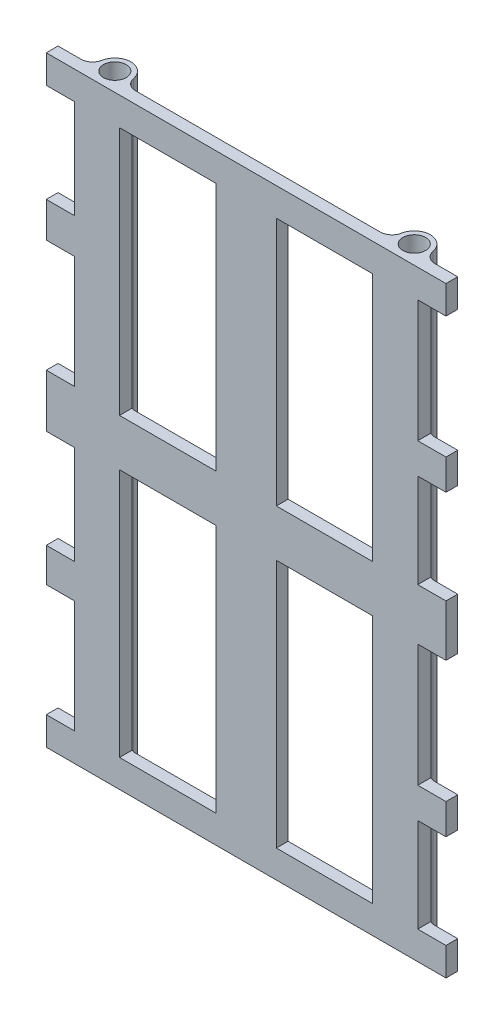
SolidWorks part; units mm, degrees
material "E-Glass Fiber"
ref_plane "Front Plane" through (0, 0, 0) normal (0, 0, 1) x (1, 0, 0)
ref_plane "Top Plane" through (0, 0, 0) normal (0, 1, 0) x (1, 0, 0)
ref_plane "Right Plane" through (0, 0, 0) normal (1, 0, 0) x (0, 0, -1)
other "Center of Mass"
sketch "Sketch1" plane through (0, 0, 0) normal (0, 1, 0) x (1, 0, 0)
  line L19 (85, -5) -> (85, 0)
  line L20 (85, -5) -> (-85, -5)
  line L24 (85, 0) -> (75.3042, 0)
  line L25 (-85, -5) -> (-85, 0)
  line L26 (85, -5) -> (-85, 0) construction
  line L27 (85, 0) -> (-85, -5) construction
  line L28 (0, 0) -> (0, -5) construction
  line L29 (-75.3042, 0) -> (-85, 0)
  line L30 (52.0558, 0) -> (-52.0558, 0)
  circle A29 centre (-63.68, 2.83) radius 4.825
  arc A30 (-69.8906, 0) -> (-57.4694, 0) centre (-63.68, 2.83) ccw construction
  arc A31 (-75.3042, 0) -> (-70.3891, 4.0825) centre (-75.3042, 5) ccw
  arc A32 (-56.9709, 4.0825) -> (-52.0558, 0) centre (-52.0558, 5) ccw
  arc A33 (-56.9709, 4.0825) -> (-70.3891, 4.0825) centre (-63.68, 2.83) ccw
  arc A34 (69.8906, 0) -> (57.4694, 0) centre (63.68, 2.83) cw construction
  arc A35 (56.9709, 4.0825) -> (70.3891, 4.0825) centre (63.68, 2.83) cw
  arc A36 (56.9709, 4.0825) -> (52.0558, 0) centre (52.0558, 5) cw
  arc A37 (75.3042, 0) -> (70.3891, 4.0825) centre (75.3042, 5) cw
  circle A38 centre (63.68, 2.83) radius 4.825
  point P1 (0, -2.5)
  dimension "D3" = 9.65
  dimension "D4" = 7.83
  dimension "D5" = 63.68
  dimension "D6" = 13.65
  dimension "D1" = 5
  dimension "D2" = 170
extrude "Boss-Extrude1" add sketch "Sketch1" along normal blind 255.8
sketch "Sketch2" plane through (0, 0, 0) normal (0, 0, -1) x (-1, 0, 0)
  line L0 (-85, 127.9) -> (85, 127.9) construction
  line L1 (-53.855, 11.8) -> (-12.855, 11.8)
  line L2 (-53.855, 11.8) -> (-53.855, 117.8)
  line L3 (-53.855, 243.8) -> (-12.855, 243.8)
  line L4 (-12.855, 11.8) -> (-12.855, 117.8)
  line L5 (-53.855, 11.8) -> (-12.855, 243.8) construction
  line L6 (-53.855, 243.8) -> (-12.855, 11.8) construction
  line L7 (-52.0558, 255.8) -> (52.0558, 255.8) construction
  line L8 (-12.855, 137.8) -> (-12.855, 243.8)
  line L9 (0, 255.8) -> (0, 0) construction
  line L10 (-93, 178.9) -> (-73, 178.9)
  line L11 (53.855, 11.8) -> (12.855, 11.8)
  line L12 (53.855, 11.8) -> (53.855, 117.8)
  line L13 (53.855, 243.8) -> (12.855, 243.8)
  line L14 (12.855, 11.8) -> (12.855, 117.8)
  line L15 (53.855, 11.8) -> (12.855, 243.8) construction
  line L16 (53.855, 243.8) -> (12.855, 11.8) construction
  line L17 (-58.855, 0) -> (-58.855, 255.8) construction
  line L18 (58.855, 255.8) -> (58.855, 0) construction
  line L19 (12.855, 137.8) -> (12.855, 243.8)
  line L20 (-53.855, 117.8) -> (-12.855, 117.8)
  line L22 (-53.855, 137.8) -> (-12.855, 137.8)
  line L24 (12.855, 137.8) -> (53.855, 137.8)
  line L25 (12.855, 117.8) -> (53.855, 117.8)
  line L26 (-53.855, 137.8) -> (-53.855, 243.8)
  line L27 (53.855, 137.8) -> (53.855, 243.8)
  line L28 (-93, 178.9) -> (-93, 138.9)
  line L29 (-93, 138.9) -> (-73, 138.9)
  line L30 (-73, 178.9) -> (-73, 138.9)
  line L31 (-93, 178.9) -> (-73, 138.9) construction
  line L32 (-93, 138.9) -> (-73, 178.9) construction
  line L33 (-85, 255.8) -> (-85, 0) construction
  line L34 (85, 255.8) -> (85, 0) construction
  line L35 (-93, 52) -> (-73, 52)
  line L36 (-73, 191.9) -> (-93, 191.9)
  line L37 (-73, 191.9) -> (-73, 243.8)
  line L38 (-73, 243.8) -> (-93, 243.8)
  line L39 (-93, 191.9) -> (-93, 243.8)
  line L40 (-73, 191.9) -> (-93, 243.8) construction
  line L41 (-73, 243.8) -> (-93, 191.9) construction
  line L42 (-93, 52) -> (-93, 12)
  line L43 (-93, 12) -> (-73, 12)
  line L44 (-73, 52) -> (-73, 12)
  line L53 (-93, 52) -> (-73, 12) construction
  line L54 (-93, 12) -> (-73, 52) construction
  line L55 (-73, 65) -> (-93, 65)
  line L56 (-73, 65) -> (-73, 117)
  line L57 (-73, 117) -> (-93, 117)
  line L58 (-93, 65) -> (-93, 117)
  line L59 (-73, 65) -> (-93, 117) construction
  line L60 (-73, 117) -> (-93, 65) construction
  line L61 (75.3042, 255.8) -> (85, 255.8) construction
  line L62 (-85, 0) -> (-75.3042, 0) construction
  line L67 (93, 201.8) -> (73, 201.8)
  line L68 (93, 201.8) -> (93, 243.8)
  line L73 (93, 243.8) -> (73, 243.8)
  line L74 (73, 201.8) -> (73, 243.8)
  line L75 (-85, 255.8) -> (-75.3042, 255.8) construction
  line L76 (93, 74.4) -> (73, 74.4)
  line L77 (93, 201.8) -> (73, 243.8) construction
  line L78 (93, 243.8) -> (73, 201.8) construction
  line L83 (73, 138.9) -> (93, 138.9)
  line L84 (73, 138.9) -> (73, 186.8)
  line L85 (73, 186.8) -> (93, 186.8)
  line L86 (93, 138.9) -> (93, 186.8)
  line L87 (73, 138.9) -> (93, 186.8) construction
  line L88 (73, 186.8) -> (93, 138.9) construction
  line L89 (93, 74.4) -> (93, 116.4)
  line L90 (93, 116.4) -> (73, 116.4)
  line L91 (73, 74.4) -> (73, 116.4)
  line L92 (93, 74.4) -> (73, 116.4) construction
  line L93 (93, 116.4) -> (73, 74.4) construction
  line L94 (73, 12) -> (93, 12)
  line L95 (73, 12) -> (73, 59.9)
  line L96 (73, 59.9) -> (93, 59.9)
  line L97 (93, 12) -> (93, 59.9)
  line L98 (73, 12) -> (93, 59.9) construction
  line L99 (73, 59.9) -> (93, 12) construction
  line L100 (75.3042, 0) -> (85, 0) construction
  point P0 (-33.355, 127.8)
  point P5 (-83, 158.9)
  point P14 (33.355, 127.8)
  point P23 (0, 127.8)
  point P39 (-83, 217.85)
  point P44 (-83, 32)
  point P49 (-83, 91)
  point P54 (83, 222.8)
  point P61 (83, 162.85)
  point P70 (83, 95.4)
  point P75 (83, 35.95)
  dimension "D1" = 12
  dimension "D2" = 5
  dimension "D3" = 41
  dimension "D4" = 12
  dimension "D5" = 5
  dimension "D6" = 41
  dimension "D7" = 20
  dimension "D8" = 11
  dimension "D9" = 40
  dimension "D10" = 73
  dimension "D11" = 20
  dimension "D12" = 13
  dimension "D13" = 12
  dimension "D14" = 40
  dimension "D15" = 20
  dimension "D16" = 13
  dimension "D17" = 52
  dimension "D18" = 73
  dimension "D19" = 20
  dimension "D20" = 12
  dimension "D21" = 12
  dimension "D22" = 15
  dimension "D23" = 42
  dimension "D24" = 73
  dimension "D25" = 11
  dimension "D26" = 20
  dimension "D27" = 14.5
  dimension "D28" = 42
  dimension "D29" = 73
  dimension "D30" = 12
extrude "Cut-Extrude2" cut sketch "Sketch2" against normal through all and the other way through all
equation "\"rod_d\"= 9.65"
equation "\"big_bearing_id\"= 140mm"
equation "\"rod_offset_c2c\"= \"big_bearing_id\" / 2 - \"rod_d\" / 2 - 1.5"
